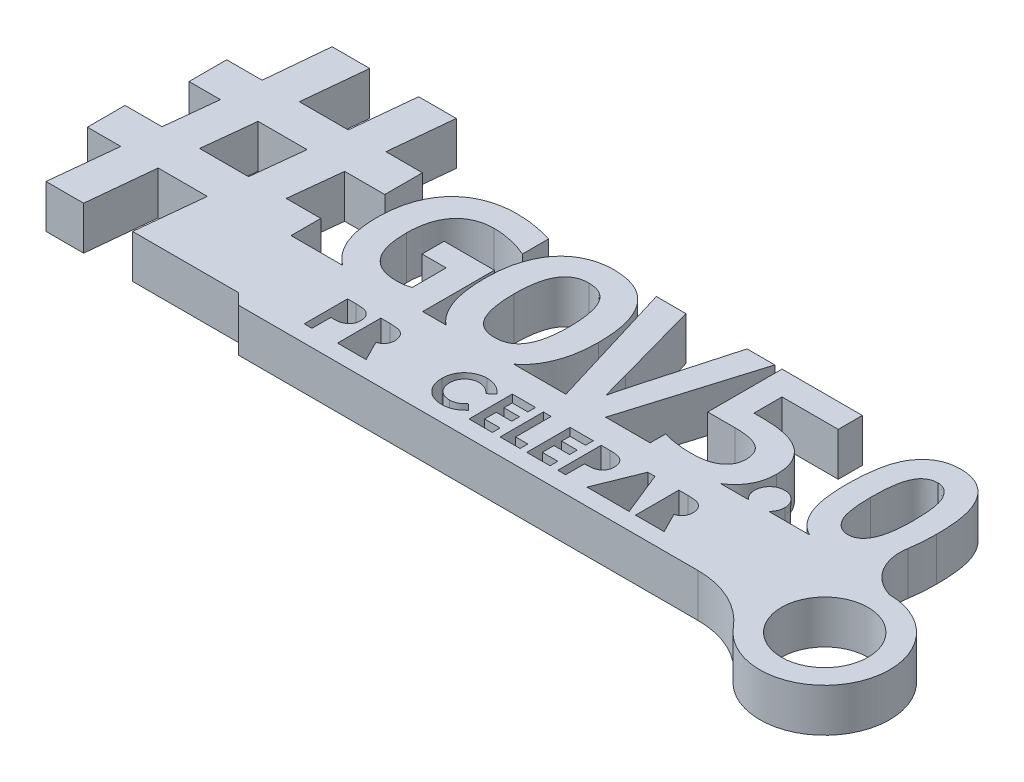
SolidWorks part; units mm, degrees
ref_plane "Front Plane" through (0, 0, 0) normal (0, 0, 1) x (1, 0, 0)
ref_plane "Top Plane" through (0, 0, 0) normal (0, 1, 0) x (1, 0, 0)
ref_plane "Right Plane" through (0, 0, 0) normal (1, 0, 0) x (0, 0, -1)
sketch "Sketch1" plane through (0, 0, 0) normal (0, 1, 0) x (1, 0, 0)
  text T0 "<b>#</b>" font "Consolas" height 30
extrude "Boss-Extrude1" add sketch "Sketch1" along normal blind 5
sketch "Sketch2" plane through (0, 5, 0) normal (0, 1, 0) x (1, 0, 0)
  text T0 "<b>GOV5</b>" font "Consolas" height 16
extrude "Boss-Extrude2" add sketch "Sketch2" against normal blind 5 separate body
sketch "Sketch3" plane through (0, 5, 0) normal (0, 1, 0) x (1, 0, 0)
  line L0 (62.3851, 9.3354) -> (58.3996, 9.3354) construction
  line L1 (20.2873, 10.3354) -> (90.3172, 10.3354)
  line L2 (20.2873, 10.3354) -> (20.2873, 0.3354)
  line L3 (20.2873, 0.3354) -> (90.3172, 0.3354)
  line L4 (90.3172, 10.3354) -> (90.3172, 0.3354)
  dimension "D1" = 10
  dimension "D2" = 1
extrude "Boss-Extrude3" add sketch "Sketch3" against normal blind 5
sketch "Sketch4" plane through (0, 5, 0) normal (0, 1, 0) x (1, 0, 0)
  text T0 "." font "Century Gothic" height 16
extrude "Boss-Extrude5" add sketch "Sketch4" against normal blind 5
sketch "Sketch5" plane through (0, 5, 0) normal (0, 1, 0) x (1, 0, 0)
  text T0 "0" font "Century Gothic" height 15
extrude "Boss-Extrude6" add sketch "Sketch5" against normal blind 5
sketch "Sketch8" plane through (0, 5, 0) normal (0, 1, 0) x (1, 0, 0)
  circle A0 centre (96.8593, 1.47) radius 7.5
  circle A1 centre (96.8593, 1.47) radius 5
  dimension "D1" = 10
  dimension "D2" = 15
extrude "Boss-Extrude9" add sketch "Sketch8" against normal blind 5 contours A0 | A1
fillet "Fillet1" radius 10 1 edges at (89.4456, 2.5, -0.3354)
fillet "Fillet2" radius 10 1 edges at (90.3172, 2.5, -5.1375)
sketch "Sketch10" plane through (0, 5, 0) normal (0, 1, 0) x (1, 0, 0)
  line L1 (96.8593, 8.97) -> (91.345, 10.8091)
  line L2 (91.345, 10.8091) -> (90.3172, 10.2035)
  line L3 (90.3172, 10.2035) -> (91.1882, 6.19)
  line L4 (91.1882, 6.19) -> (96.8593, 8.97)
  arc A0 (91.0732, -3.302) -> (96.1737, 8.9386) centre (96.8593, 1.47) ccw construction
  spline S0 degree 3 poles (93.507, 17.759) (93.5056, 17.5166) (93.5028, 17.0455) (93.4728, 16.36) (93.4212, 15.7157) (93.3546, 15.1129) (93.2635, 14.5517) (93.1567, 14.0307) (93.0298, 13.5502) (92.8766, 13.1112) (92.7118, 12.7066) (92.5304, 12.3316) (92.3356, 11.9852) (92.1319, 11.6621) (91.9081, 11.3719) (91.6751, 11.1047) (91.4227, 10.8707) (91.1617, 10.6578) (90.8823, 10.4739) (90.6012, 10.3204) (90.4082, 10.2389) (90.3172, 10.2035) knots 0 0 0 0 0.068491 0.133077 0.193829 0.251083 0.304401 0.354408 0.401295 0.444701 0.485692 0.524676 0.562307 0.597947 0.632474 0.665752 0.697985 0.729586 0.760825 0.792355 0.819946 0.819946 0.819946 0.819946 construction
  point P3 (91.345, 10.8091)
extrude "Boss-Extrude11" add sketch "Sketch10" against normal blind 5 contours L1 L2 L3 L4
sketch "Sketch11" plane through (0, 5, 0) normal (0, 1, 0) x (1, 0, 0)
  text T0 "<b>PR   CELEPAR</b>" font "Century Gothic" height 5
extrude "Cut-Extrude1" cut sketch "Sketch11" against normal blind 10
sketch "Sketch12" plane through (0, 5, 0) normal (0, 1, 0) x (1, 0, 0)
  line L0 (69.9603, 3.8463) -> (72.4847, 3.8463)
  line L1 (74.637, 6.5758) -> (76.6823, 6.5758)
  line L2 (74.637, 6.5758) -> (74.637, 5.0712)
  line L3 (74.637, 5.0712) -> (76.6823, 5.0712)
  line L4 (76.6823, 6.5758) -> (76.6823, 5.0712)
  line L5 (65.7686, 6.5758) -> (67.5053, 6.5758)
  line L6 (65.7686, 6.5758) -> (65.7686, 5.0712)
  line L7 (65.7686, 5.0712) -> (67.5053, 5.0712)
  line L8 (67.5053, 6.5758) -> (67.5053, 5.0712)
  line L9 (72.4847, 3.8463) -> (71.2225, 6.5758)
  line L10 (71.2225, 6.5758) -> (69.9603, 3.8463)
  line L11 (40.6846, 6.3674) -> (40.6846, 5.3418)
  line L12 (40.6846, 5.3418) -> (42.1348, 5.3418)
  line L13 (42.1348, 5.3418) -> (42.1348, 6.3674)
  line L14 (42.1348, 6.3674) -> (40.6846, 6.3674)
  line L15 (36.8384, 6.3674) -> (36.8384, 5.3418)
  line L16 (37.1209, 6.3674) -> (36.8384, 6.3674) construction
  line L17 (36.8384, 5.3418) -> (37.1559, 5.3418) construction
  line L18 (36.8384, 6.3674) -> (36.8384, 5.3418) construction
  line L19 (36.8384, 5.3418) -> (38.1863, 5.3418)
  line L20 (38.1863, 5.3418) -> (38.1863, 6.3674)
  line L21 (38.1863, 6.3674) -> (36.8384, 6.3674)
extrude "Cut-Extrude2" cut sketch "Sketch12" against normal blind 10
sketch "Sketch14" plane through (0, 5, 0) normal (0, 1, 0) x (1, 0, 0)
  line L0 (74.915, 2.2649) -> (77.0127, 2.2649)
  line L1 (75.1077, 2.2649) -> (74.2102, 2.2649) construction
  line L2 (77.5115, 2.2649) -> (76.5139, 2.2649) construction
  line L3 (77.0127, 2.2649) -> (75.4804, 5.1419)
  line L4 (75.4804, 5.1419) -> (74.915, 5.1419)
  line L5 (74.915, 5.1419) -> (74.915, 2.2649)
  line L6 (72.5145, 2.2649) -> (69.5588, 2.2649)
  line L7 (69.5588, 2.2649) -> (69.9474, 3.2905)
  line L8 (69.9474, 3.2905) -> (72.1259, 3.2905)
  line L9 (72.1259, 3.2905) -> (72.5145, 2.2649)
  line L10 (40.6846, 2.2649) -> (42.0908, 2.2649)
  line L11 (42.0908, 2.2649) -> (40.9891, 4.4444)
  line L12 (40.9891, 4.4444) -> (40.6846, 4.4444)
  line L13 (40.6846, 4.4444) -> (40.6846, 2.2649)
extrude "Cut-Extrude3" cut sketch "Sketch14" against normal blind 10
chamfer "Chamfer1" distance 10 angle 45 1 edges at (20.2873, 2.5, -0.3354)
fillet "Fillet3" radius 5 1 edges at (91.345, 2.5, -10.8091)
